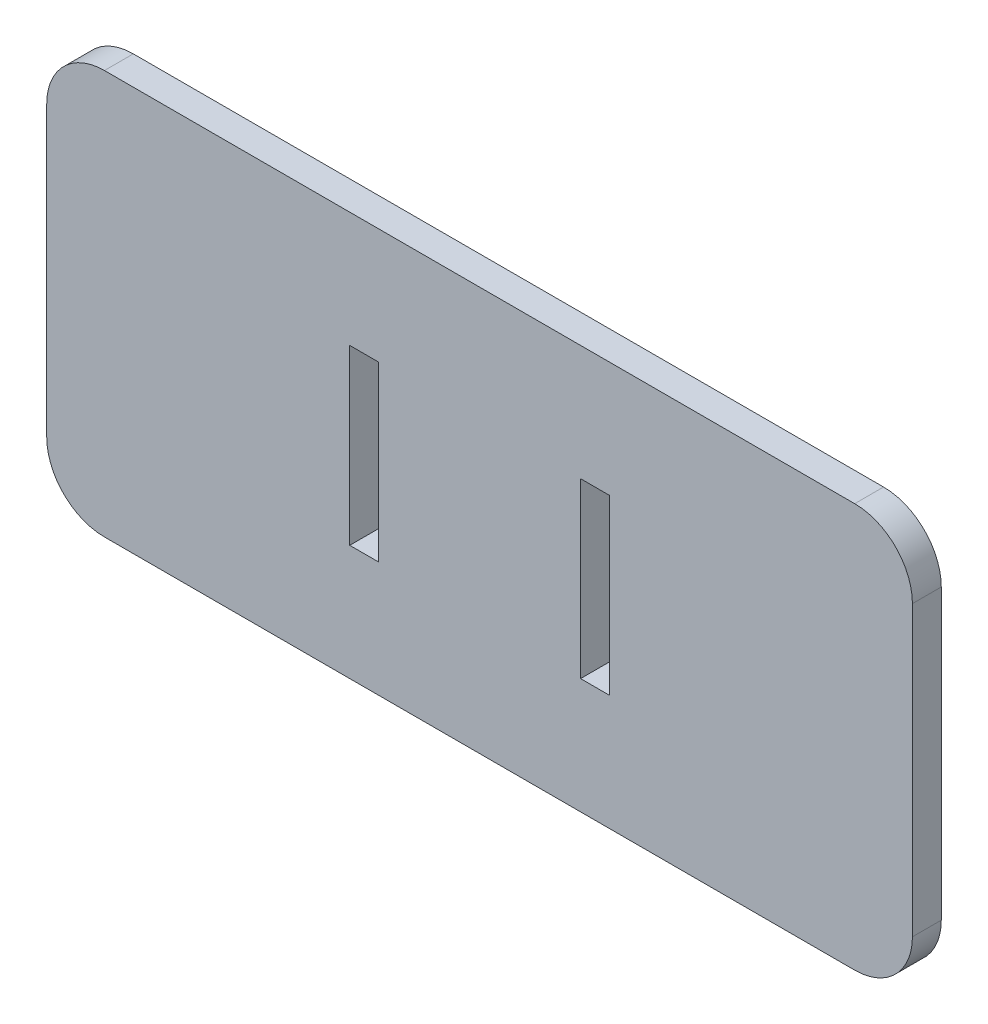
SolidWorks part; units mm, degrees
ref_plane "Front Plane" through (0, 0, 0) normal (0, 0, 1) x (1, 0, 0)
ref_plane "Top Plane" through (0, 0, 0) normal (0, 1, 0) x (1, 0, 0)
ref_plane "Right Plane" through (0, 0, 0) normal (1, 0, 0) x (0, 0, -1)
sketch "Sketch1" plane through (0, 0, 0) normal (0, 0, 1) x (1, 0, 0)
  line L1 (80, 40) -> (-180, 40)
  line L2 (100, 20) -> (100, -80)
  line L3 (80, -100) -> (-180, -100)
  line L4 (-200, 20) -> (-200, -80)
  arc A0 (80, 40) -> (100, 20) centre (80, 20) cw
  arc A1 (100, -80) -> (80, -100) centre (80, -80) cw
  arc A2 (-180, -100) -> (-200, -80) centre (-180, -80) cw
  arc A3 (-180, 40) -> (-200, 20) centre (-180, 20) ccw
  point P0 (0, 0)
  point P10 (100, -100)
  point P13 (-200, -100)
  point P16 (-200, 40)
  dimension "D3" = 20
  dimension "D1" = 300
  dimension "D2" = 140
extrude "Boss-Extrude1" add sketch "Sketch1" along normal blind 10
sketch "Sketch2" plane through (0, 0, 10) normal (0, 0, 1) x (1, 0, 0)
  line L0 (-200, -30) -> (100, -30) construction
  line L1 (-200, 20) -> (-200, -80) construction
  line L2 (100, -80) -> (100, 20) construction
  line L3 (-90, -30) -> (-10, -30) construction
  line L4 (-95, -60) -> (-85, -60)
  line L5 (-95, -60) -> (-95, 0)
  line L6 (-95, 0) -> (-85, 0)
  line L7 (-85, -60) -> (-85, 0)
  line L8 (-95, -60) -> (-85, 0) construction
  line L9 (-95, 0) -> (-85, -60) construction
  line L10 (-15, -60) -> (-5, -60)
  line L11 (-15, -60) -> (-15, 0)
  line L12 (-15, 0) -> (-5, 0)
  line L13 (-5, -60) -> (-5, 0)
  line L14 (-15, -60) -> (-5, 0) construction
  line L15 (-15, 0) -> (-5, -60) construction
  point P6 (-90, -30)
  point P11 (-10, -30)
  point P18 (-50, -30)
  point P19 (-50, -30)
  dimension "D1" = 70
  dimension "D2" = 10
  dimension "D3" = 60
extrude "Cut-Extrude1" cut sketch "Sketch2" against normal blind 10
